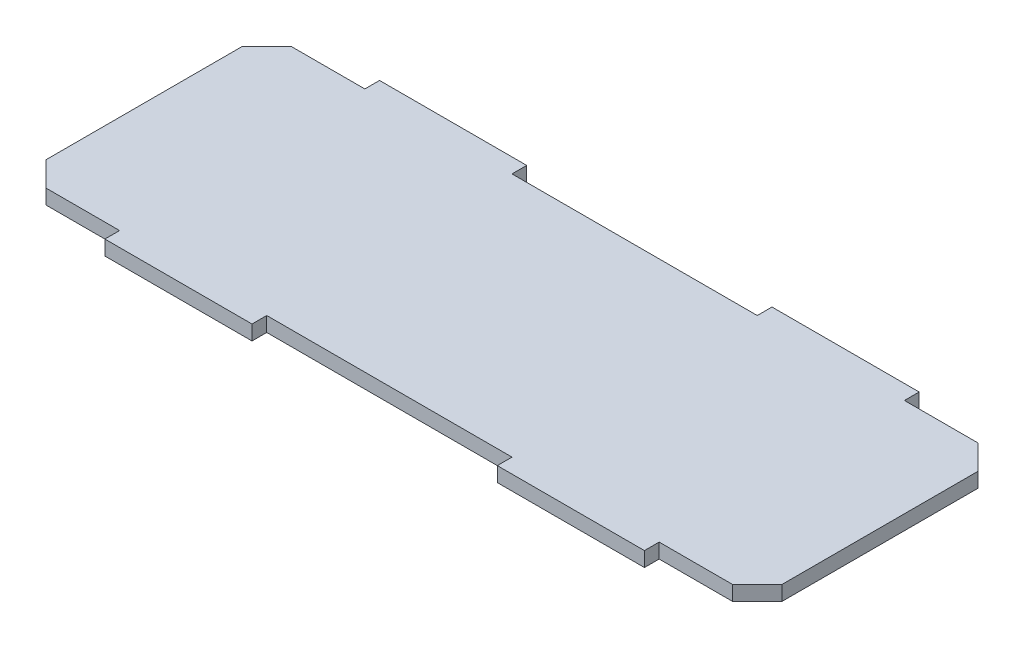
SolidWorks part; units mm, degrees
ref_plane "Alzado" through (0, 0, 0) normal (0, 0, 1) x (1, 0, 0)
ref_plane "Planta" through (0, 0, 0) normal (0, 1, 0) x (1, 0, 0)
ref_plane "Vista lateral" through (0, 0, 0) normal (1, 0, 0) x (0, 0, -1)
sketch "Croquis1" plane through (0, 0, 0) normal (0, 1, 0) x (1, 0, 0)
  line L1 (-70, -25) -> (-55, -25)
  line L2 (-75, -20) -> (-75, 20)
  line L3 (-70, 25) -> (-55, 25)
  line L4 (75, -20) -> (75, 20)
  line L5 (-75, -25) -> (75, 25) construction
  line L6 (-75, 25) -> (75, -25) construction
  line L8 (-55, 25) -> (-55, 28)
  line L9 (-55, 28) -> (-25, 28)
  line L10 (-25, 25) -> (-25, 28)
  line L12 (-55, -25) -> (-55, -28)
  line L13 (-55, -28) -> (-25, -28)
  line L14 (-25, -25) -> (-25, -28)
  line L16 (25, 25) -> (25, 28)
  line L17 (25, 28) -> (55, 28)
  line L18 (55, 25) -> (55, 28)
  line L20 (25, -25) -> (25, -28)
  line L21 (25, -28) -> (55, -28)
  line L22 (55, -25) -> (55, -28)
  line L24 (55, -25) -> (70, -25)
  line L25 (55, 25) -> (70, 25)
  line L26 (0, 0) -> (0, 53.7468) construction
  line L27 (-75, 20) -> (-70, 25)
  line L28 (-75, -20) -> (-70, -25)
  line L29 (70, -25) -> (75, -20)
  line L30 (70, 25) -> (75, 20)
  line L55 (-25, 25) -> (25, 25)
  line L56 (-25, -25) -> (25, -25)
  point P0 (0, 0)
  point P22 (-40, 28)
  point P23 (-40, -28)
  point P26 (40, 28)
  dimension "D1" = 50
  dimension "D2" = 150
  dimension "D3" = 40
  dimension "D4" = 30
  dimension "D5" = 40
  dimension "D6" = 3
extrude "Saliente-Extruir1" add sketch "Croquis1" along normal blind 3
